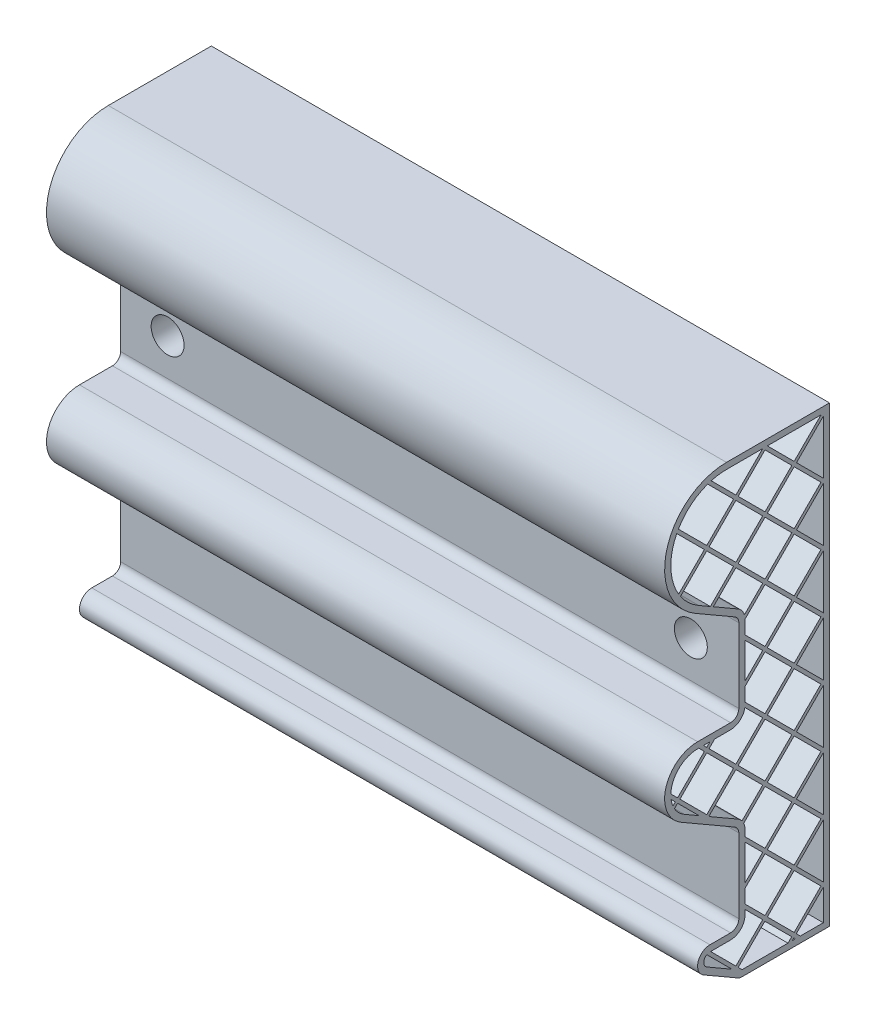
SolidWorks part; units mm, degrees
ref_plane "Front" through (0, 0, 0) normal (0, 0, 1) x (1, 0, 0)
ref_plane "Top" through (0, 0, 0) normal (0, 1, 0) x (1, 0, 0)
ref_plane "Right" through (0, 0, 0) normal (1, 0, 0) x (0, 0, -1)
sketch "Croquis1" plane through (0, 0, 0) normal (1, 0, 0) x (0, 0, -1)
  line L1 (0, 0) -> (-21.2539, 0)
  line L2 (0, 0) -> (0, 110)
  line L3 (0, 110) -> (-25, 110)
  line L5 (-32, 54.7927) -> (-24, 54.7927)
  line L10 (-22, 74.7927) -> (-22, 56.7927)
  line L14 (-22, 12.6269) -> (-22, 30.6269)
  line L16 (-36, 39.8645) -> (-23, 32.359)
  line L17 (-29, 10.6269) -> (-24, 10.6269)
  line L18 (-32.5, 82.0096) -> (-23, 76.5248)
  line L19 (-30.5, 5.0289) -> (-22.2539, 0.2679)
  arc A2 (-25, 110) -> (-32.5, 82.0096) centre (-25, 95) ccw
  arc A3 (-29, 10.6269) -> (-30.5, 5.0289) centre (-29, 7.6269) ccw
  arc A6 (-32, 54.7927) -> (-36, 39.8645) centre (-32, 46.7927) ccw
  arc A8 (-23, 76.5248) -> (-22, 74.7927) centre (-24, 74.7927) cw
  arc A9 (-22, 56.7927) -> (-24, 54.7927) centre (-24, 56.7927) cw
  arc A10 (-23, 32.359) -> (-22, 30.6269) centre (-24, 30.6269) cw
  arc A11 (-22, 12.6269) -> (-24, 10.6269) centre (-24, 12.6269) cw
  arc A12 (-21.2539, 0) -> (-22.2539, 0.2679) centre (-21.2539, 2) cw
  point P0 (0, 0)
  point P11 (-22, 54.7927)
  dimension "D1" = 2
  dimension "D2" = 15
  dimension "D8" = 8
  dimension "D9" = 30
  dimension "D12" = 2
  dimension "D7" = 2
  dimension "D10" = 2
  dimension "D11" = 2
  dimension "D16" = 18
  dimension "D19" = 110
  dimension "D14" = 10
  dimension "D6" = 3
  dimension "D3" = 40
  dimension "D4" = 30
  dimension "D5" = 18
  dimension "D13" = 30
  dimension "D17" = 20
  dimension "D18" = 20
extrude "Saliente-Extruir1" add sketch "Croquis1" along normal blind 150
sketch "Croquis2" plane through (150, 0, 0) normal (1, 0, 0) x (0, 0, -1)
  line L30 (-24, 53.2927) -> (-32, 53.2927)
  line L31 (-35.25, 41.1636) -> (-22.25, 33.658)
  line L32 (-20.5, 30.6269) -> (-20.5, 12.6269)
  line L33 (-24, 9.1269) -> (-29, 9.1269)
  line L34 (-29.75, 6.3279) -> (-21.5039, 1.567)
  line L35 (-21.2539, 1.5) -> (-1.5, 1.5)
  line L36 (-1.5, 1.5) -> (-1.5, 108.5)
  line L37 (-1.5, 108.5) -> (-25, 108.5)
  line L38 (-31.75, 83.3087) -> (-22.25, 77.8238)
  line L39 (-20.5, 74.7927) -> (-20.5, 56.7927)
  line L40 (-24, 53.2927) -> (-32, 53.2927)
  line L41 (-35.25, 41.1636) -> (-22.25, 33.658)
  line L42 (-20.5, 30.6269) -> (-20.5, 12.6269)
  line L43 (-24, 9.1269) -> (-29, 9.1269)
  line L44 (-29.75, 6.3279) -> (-21.5039, 1.567)
  line L45 (-21.2539, 1.5) -> (-1.5, 1.5)
  line L46 (-1.5, 1.5) -> (-1.5, 108.5)
  line L47 (-1.5, 108.5) -> (-25, 108.5)
  line L48 (-31.75, 83.3087) -> (-22.25, 77.8238)
  line L49 (-20.5, 74.7927) -> (-20.5, 56.7927)
  arc A24 (-24, 53.2927) -> (-20.5, 56.7927) centre (-24, 56.7927) ccw
  arc A25 (-32, 53.2927) -> (-35.25, 41.1636) centre (-32, 46.7927) ccw
  arc A26 (-20.5, 30.6269) -> (-22.25, 33.658) centre (-24, 30.6269) ccw
  arc A27 (-24, 9.1269) -> (-20.5, 12.6269) centre (-24, 12.6269) ccw
  arc A28 (-29, 9.1269) -> (-29.75, 6.3279) centre (-29, 7.6269) ccw
  arc A29 (-21.5039, 1.567) -> (-21.2539, 1.5) centre (-21.2539, 2) ccw
  arc A30 (-25, 108.5) -> (-31.75, 83.3087) centre (-25, 95) ccw
  arc A31 (-20.5, 74.7927) -> (-22.25, 77.8238) centre (-24, 74.7927) ccw
  arc A32 (-24, 53.2927) -> (-20.5, 56.7927) centre (-24, 56.7927) ccw
  arc A33 (-32, 53.2927) -> (-35.25, 41.1636) centre (-32, 46.7927) ccw
  arc A34 (-20.5, 30.6269) -> (-22.25, 33.658) centre (-24, 30.6269) ccw
  arc A35 (-24, 9.1269) -> (-20.5, 12.6269) centre (-24, 12.6269) ccw
  arc A36 (-29, 9.1269) -> (-29.75, 6.3279) centre (-29, 7.6269) ccw
  arc A37 (-21.5039, 1.567) -> (-21.2539, 1.5) centre (-21.2539, 2) ccw
  arc A38 (-25, 108.5) -> (-31.75, 83.3087) centre (-25, 95) ccw
  arc A39 (-20.5, 74.7927) -> (-22.25, 77.8238) centre (-24, 74.7927) ccw
  dimension "D1" = 1.5
sketch "Croquis3" plane through (150, 0, 0) normal (1, 0, 0) x (0, 0, -1)
  line L0 (-29.1353, 107.851) -> (-1.5, 80.2157)
  line L1 (-1.5, 108.5) -> (-25, 108.5) construction
  line L2 (-15.6421, 108.5) -> (-1.5, 94.3579)
  line L3 (-1.5, 1.5) -> (-1.5, 108.5) construction
  line L4 (-36.8654, 101.439) -> (-1.5, 66.0736)
  line L5 (-1.5, 51.9315) -> (-20.5, 70.9315)
  line L6 (-1.5, 37.7893) -> (-20.5, 56.7893)
  line L7 (-1.5, 23.6472) -> (-31.1456, 53.2927)
  line L8 (-1.5, 9.5051) -> (-38.4933, 46.4984)
  line L9 (-7.6371, 1.5) -> (-20.5, 14.3629)
  line L10 (-21.2539, 1.5) -> (-1.5, 1.5) construction
  line L11 (-20.5, 74.7927) -> (-20.5, 56.7927) construction
  line L12 (-24, 53.2927) -> (-32, 53.2927) construction
  line L13 (-20.5, 30.6269) -> (-20.5, 12.6269) construction
  line L14 (-22.3139, 2.0346) -> (-29.4062, 9.1269)
  line L15 (-29.75, 6.3279) -> (-21.5039, 1.567) construction
  line L16 (-24, 9.1269) -> (-29, 9.1269) construction
  line L17 (-1.5, 108.5) -> (-28.5429, 81.4571)
  line L18 (-36.3896, 87.7525) -> (-15.6421, 108.5)
  line L19 (-20.5397, 75.3182) -> (-1.5, 94.3579)
  line L20 (-37.8191, 43.8966) -> (-1.5, 80.2157)
  line L21 (-29.6457, 37.9279) -> (-1.5, 66.0736)
  line L22 (-20.5, 32.9315) -> (-1.5, 51.9315)
  line L23 (-31.786, 7.5034) -> (-1.5, 37.7893)
  line L24 (-22.8202, 2.327) -> (-1.5, 23.6472)
  line L25 (-9.5051, 1.5) -> (-1.5, 9.5051)
  line L26 (-31.75, 83.3087) -> (-22.25, 77.8238) construction
  line L27 (-35.25, 41.1636) -> (-22.25, 33.658) construction
  arc A0 (-25, 108.5) -> (-31.75, 83.3087) centre (-25, 95) ccw construction
  arc A1 (-24, 53.2927) -> (-20.5, 56.7927) centre (-24, 56.7927) ccw construction
  arc A2 (-32, 53.2927) -> (-35.25, 41.1636) centre (-32, 46.7927) ccw construction
  arc A3 (-20.5, 74.7927) -> (-22.25, 77.8238) centre (-24, 74.7927) ccw construction
  dimension "D1" = 45
  dimension "D2" = 10
  dimension "D4" = 10
  dimension "D5" = 10
  dimension "D6" = 10
  dimension "D7" = 10
  dimension "D8" = 10
  dimension "D9" = 10
  dimension "D10" = 10
  dimension "D11" = 45
  dimension "D12" = 10
sketch "Croquis4" plane through (150, 0, 0) normal (1, 0, 0) x (0, 0, -1)
  line L68 (-22.8202, 2.327) -> (-1.5, 23.6472) construction
  line L69 (-9.5051, 1.5) -> (-1.5, 9.5051) construction
  line L70 (-22.3139, 2.0346) -> (-29.4062, 9.1269) construction
  line L71 (-7.6371, 1.5) -> (-20.5, 14.3629) construction
  line L72 (-31.786, 7.5034) -> (-1.5, 37.7893) construction
  line L73 (-1.5, 9.5051) -> (-38.4933, 46.4984) construction
  line L74 (-1.5, 23.6472) -> (-31.1456, 53.2927) construction
  line L75 (-1.5, 37.7893) -> (-20.5, 56.7893) construction
  line L76 (-29.6457, 37.9279) -> (-1.5, 66.0736) construction
  line L77 (-1.5, 51.9315) -> (-20.5, 70.9315) construction
  line L78 (-37.8191, 43.8966) -> (-1.5, 80.2157) construction
  line L79 (-20.5397, 75.3182) -> (-1.5, 94.3579) construction
  line L80 (-1.5, 108.5) -> (-28.5429, 81.4571) construction
  line L81 (-15.6421, 108.5) -> (-1.5, 94.3579) construction
  line L82 (-36.3896, 87.7525) -> (-15.6421, 108.5) construction
  line L83 (-36.8654, 101.439) -> (-1.5, 66.0736) construction
  line L84 (-29.1353, 107.851) -> (-1.5, 80.2157) construction
  line L119 (-20.5, 32.9315) -> (-1.5, 51.9315) construction
  line L120 (-1.5, 51.9315) -> (-20.5, 70.9315)
  line L121 (-20.5, 32.9315) -> (-1.5, 51.9315)
  line L122 (-36.8654, 101.439) -> (-1.5, 66.0736)
  line L123 (-29.6457, 37.9279) -> (-1.5, 66.0736)
  line L124 (-29.1353, 107.851) -> (-1.5, 80.2157)
  line L125 (-37.8191, 43.8966) -> (-1.5, 80.2157)
  line L126 (-20.5397, 75.3182) -> (-1.5, 94.3579)
  line L127 (-15.6421, 108.5) -> (-1.5, 94.3579)
  line L128 (-36.3896, 87.7525) -> (-15.6421, 108.5)
  line L129 (-7.6371, 1.5) -> (-20.5, 14.3629)
  line L130 (-1.5, 9.5051) -> (-38.4933, 46.4984)
  line L131 (-9.5051, 1.5) -> (-1.5, 9.5051)
  line L132 (-1.5, 23.6472) -> (-31.1456, 53.2927)
  line L133 (-22.8202, 2.327) -> (-1.5, 23.6472)
  line L134 (-1.5, 37.7893) -> (-20.5, 56.7893)
  line L135 (-31.786, 7.5034) -> (-1.5, 37.7893)
  line L136 (-1.5, 108.5) -> (-28.5429, 81.4571)
  line L137 (-22.3139, 2.0346) -> (-29.4062, 9.1269)
  line L138 (-36.1068, 87.4697) -> (-15.6421, 107.9343)
  line L139 (-15.6421, 107.9343) -> (-2.0657, 94.3579)
  line L140 (-20.8225, 75.601) -> (-2.0657, 94.3579)
  line L141 (-29.4182, 107.5682) -> (-2.0657, 80.2157)
  line L142 (-38.102, 44.1794) -> (-2.0657, 80.2157)
  line L143 (-37.1483, 101.1562) -> (-1.7828, 65.7908)
  line L144 (-1.7828, 108.7828) -> (-28.8258, 81.7399)
  line L145 (-36.6725, 88.0353) -> (-15.6421, 109.0657)
  line L146 (-15.6421, 109.0657) -> (-0.9343, 94.3579)
  line L147 (-20.2568, 75.0354) -> (-0.9343, 94.3579)
  line L148 (-28.8525, 108.1339) -> (-0.9343, 80.2157)
  line L149 (-37.5363, 43.6138) -> (-0.9343, 80.2157)
  line L150 (-36.5826, 101.7219) -> (-1.2172, 66.3564)
  line L151 (-1.2172, 108.2172) -> (-28.2601, 81.1742)
  line L152 (-20.2172, 32.6486) -> (-0.9343, 51.9315)
  line L153 (-0.9343, 51.9315) -> (-20.2172, 71.2143)
  line L154 (-29.3628, 37.6451) -> (-1.2172, 65.7908)
  line L155 (-1.2172, 38.0722) -> (-20.2172, 57.0722)
  line L156 (-1.2172, 23.93) -> (-30.8627, 53.5756)
  line L157 (-20.7828, 33.2143) -> (-2.0657, 51.9315)
  line L158 (-2.0657, 51.9315) -> (-20.7828, 70.6486)
  line L159 (-29.9285, 38.2108) -> (-1.7828, 66.3564)
  line L160 (-1.7828, 37.5065) -> (-20.7828, 56.5065)
  line L161 (-1.7828, 23.3643) -> (-31.4284, 53.0099)
  line L162 (-9.2222, 1.2172) -> (-0.9343, 9.5051)
  line L163 (-0.9343, 9.5051) -> (-38.2105, 46.7812)
  line L164 (-31.5031, 7.2205) -> (-1.2172, 37.5065)
  line L165 (-22.5374, 2.0441) -> (-1.2172, 23.3643)
  line L166 (-7.3542, 1.7828) -> (-20.2172, 14.6458)
  line L167 (-22.031, 2.3175) -> (-29.1233, 9.4098)
  line L168 (-9.7879, 1.7828) -> (-2.0657, 9.5051)
  line L169 (-2.0657, 9.5051) -> (-38.7762, 46.2155)
  line L170 (-32.0688, 7.7862) -> (-1.7828, 38.0722)
  line L171 (-23.1031, 2.6098) -> (-1.7828, 23.93)
  line L172 (-7.9199, 1.2172) -> (-20.7828, 14.0801)
  line L173 (-22.5967, 1.7518) -> (-29.689, 8.8441)
  dimension "D1" = 0.4
  dimension "D2" = 0.4
  dimension "D3" = 0.4
  dimension "D4" = 0.4
  dimension "D5" = 0.4
  dimension "D6" = 0.4
sketch "Croquis5" plane through (150, 0, 0) normal (1, 0, 0) x (0, 0, -1)
  line L0 (-29.75, 6.3279) -> (-23.6523, 2.8074)
  line L1 (-9.7879, 1.7828) -> (-2.0657, 9.5051) construction
  line L2 (-22.5967, 1.7518) -> (-29.689, 8.8441) construction
  line L3 (-22.031, 2.3175) -> (-29.1233, 9.4098) construction
  line L4 (-22.5374, 2.0441) -> (-1.2172, 23.3643) construction
  line L5 (-23.1031, 2.6098) -> (-1.7828, 23.93) construction
  line L6 (-7.3542, 1.7828) -> (-20.2172, 14.6458) construction
  line L8 (-20.5, 30.6269) -> (-20.5, 29.0707)
  line L10 (-2.0657, 9.5051) -> (-38.7762, 46.2155) construction
  line L11 (-0.9343, 9.5051) -> (-38.2105, 46.7812) construction
  line L14 (-1.7828, 23.3643) -> (-31.4284, 53.0099) construction
  line L15 (-1.2172, 23.93) -> (-30.8627, 53.5756) construction
  line L16 (-1.7828, 37.5065) -> (-20.7828, 56.5065) construction
  line L17 (-1.2172, 38.0722) -> (-20.2172, 57.0722) construction
  line L18 (-29.9285, 38.2108) -> (-1.7828, 66.3564) construction
  line L19 (-29.3628, 37.6451) -> (-1.2172, 65.7908) construction
  line L20 (-0.9343, 51.9315) -> (-20.2172, 71.2143) construction
  line L21 (-2.0657, 51.9315) -> (-20.7828, 70.6486) construction
  line L22 (-37.5363, 43.6138) -> (-0.9343, 80.2157) construction
  line L23 (-38.102, 44.1794) -> (-2.0657, 80.2157) construction
  line L24 (-20.2568, 75.0354) -> (-0.9343, 94.3579) construction
  line L25 (-20.8225, 75.601) -> (-2.0657, 94.3579) construction
  line L26 (-1.2172, 108.2172) -> (-28.2601, 81.1742) construction
  line L27 (-1.7828, 108.7828) -> (-28.8258, 81.7399) construction
  line L28 (-15.6421, 107.9343) -> (-2.0657, 94.3579) construction
  line L29 (-15.6421, 109.0657) -> (-0.9343, 94.3579) construction
  line L30 (-36.1068, 87.4697) -> (-15.6421, 107.9343) construction
  line L31 (-36.6725, 88.0353) -> (-15.6421, 109.0657) construction
  line L32 (-37.1483, 101.1562) -> (-1.7828, 65.7908) construction
  line L33 (-36.5826, 101.7219) -> (-1.2172, 66.3564) construction
  line L34 (-28.8525, 108.1339) -> (-0.9343, 80.2157) construction
  line L35 (-29.4182, 107.5682) -> (-2.0657, 80.2157) construction
  line L37 (-10.0707, 1.5) -> (-9.1719, 2.3988)
  line L38 (-23.6523, 2.8074) -> (-29.7632, 8.9183)
  line L39 (-21.2135, 1.5) -> (-22.1475, 2.434)
  line L40 (-22.1475, 2.434) -> (-15.6773, 8.9042)
  line L41 (-22.7132, 2.9997) -> (-16.2078, 9.5051)
  line L42 (-7.0714, 1.5) -> (-8.0499, 2.4785)
  line L46 (-2.0657, 9.5051) -> (-8.5711, 16.0104)
  line L47 (-1.5, 10.0707) -> (-8.0054, 16.5761)
  line L50 (-2.0657, 23.6472) -> (-8.5711, 30.1526)
  line L51 (-1.5, 24.2129) -> (-8.0054, 30.7183)
  line L52 (-2.0657, 37.7893) -> (-8.5711, 44.2947)
  line L53 (-1.5, 38.355) -> (-8.0054, 44.8604)
  line L54 (-29.7843, 38.355) -> (-23.2789, 44.8604)
  line L55 (-29.2186, 37.7893) -> (-22.7132, 44.2947)
  line L56 (-1.5, 52.4971) -> (-8.0054, 59.0025)
  line L57 (-2.0657, 51.9315) -> (-8.5711, 58.4368)
  line L58 (-37.6211, 43.5289) -> (-36.8553, 44.2947)
  line L59 (-37.9967, 44.2847) -> (-37.421, 44.8604)
  line L60 (-20.5, 74.7922) -> (-15.6421, 79.65)
  line L61 (-20.6424, 75.7811) -> (-16.2078, 80.2157)
  line L62 (-1.5, 107.9343) -> (-8.0054, 101.4289)
  line L63 (-2.0657, 108.5) -> (-8.5711, 101.9946)
  line L64 (-15.6421, 107.9343) -> (-9.1368, 101.4289)
  line L65 (-15.0765, 108.5) -> (-8.5711, 101.9946)
  line L66 (-36.1652, 87.4113) -> (-29.7843, 93.7922)
  line L67 (-36.6051, 88.1027) -> (-30.35, 94.3579)
  line L68 (-37.0596, 101.0675) -> (-30.35, 94.3579)
  line L69 (-36.6617, 101.801) -> (-29.7843, 94.9235)
  line L70 (-28.7013, 107.9827) -> (-22.7132, 101.9946)
  line L71 (-29.5574, 107.7075) -> (-23.2789, 101.4289)
  line L72 (-22.7132, 101.9946) -> (-16.2078, 108.5)
  line L73 (-22.1475, 101.4289) -> (-15.6421, 94.9235)
  line L74 (-22.1475, 101.4289) -> (-15.6421, 107.9343)
  line L75 (-22.7132, 100.8632) -> (-16.2078, 94.3579)
  line L76 (-29.7843, 94.9235) -> (-23.2789, 101.4289)
  line L77 (-29.7843, 93.7922) -> (-23.2789, 87.2868)
  line L78 (-29.2186, 94.3579) -> (-22.7132, 87.8525)
  line L79 (-29.2186, 94.3579) -> (-22.7132, 100.8632)
  line L80 (-16.2078, 94.3579) -> (-22.7132, 87.8525)
  line L81 (-15.0765, 94.3579) -> (-8.5711, 87.8525)
  line L82 (-15.6421, 93.7922) -> (-22.1475, 87.2868)
  line L83 (-15.6421, 93.7922) -> (-9.1368, 87.2868)
  line L84 (-9.1368, 101.4289) -> (-15.6421, 94.9235)
  line L85 (-8.0054, 101.4289) -> (-1.5, 94.9235)
  line L86 (-8.5711, 100.8632) -> (-2.0657, 94.3579)
  line L87 (-8.5711, 100.8632) -> (-15.0765, 94.3579)
  line L88 (-8.5711, 87.8525) -> (-2.0657, 94.3579)
  line L89 (-8.0054, 87.2868) -> (-1.5, 80.7814)
  line L90 (-8.0054, 87.2868) -> (-1.5, 93.7922)
  line L91 (-8.5711, 86.7211) -> (-2.0657, 80.2157)
  line L92 (-23.2789, 87.2868) -> (-28.9016, 81.6641)
  line L93 (-22.7132, 86.7211) -> (-16.2078, 80.2157)
  line L94 (-22.1475, 87.2868) -> (-15.6421, 80.7814)
  line L95 (-22.7132, 86.7211) -> (-28.1843, 81.25)
  line L96 (-15.6421, 80.7814) -> (-9.1368, 87.2868)
  line L97 (-15.6421, 79.65) -> (-9.1368, 73.1447)
  line L98 (-15.0765, 80.2157) -> (-8.5711, 73.7103)
  line L99 (-15.0765, 80.2157) -> (-8.5711, 86.7211)
  line L100 (-8.5711, 73.7103) -> (-2.0657, 80.2157)
  line L101 (-8.5711, 72.579) -> (-2.0657, 66.0736)
  line L102 (-8.0054, 73.1447) -> (-1.5, 66.6393)
  line L103 (-8.0054, 73.1447) -> (-1.5, 79.65)
  line L104 (-15.6421, 66.6393) -> (-9.1368, 73.1447)
  line L105 (-16.2078, 66.0736) -> (-20.5, 70.3658)
  line L106 (-15.6421, 66.6393) -> (-20.5, 71.4971)
  line L107 (-15.0765, 66.0736) -> (-8.5711, 72.579)
  line L108 (-8.5711, 59.5682) -> (-2.0657, 66.0736)
  line L109 (-9.1368, 59.0025) -> (-15.6421, 65.5079)
  line L110 (-8.5711, 59.5682) -> (-15.0765, 66.0736)
  line L111 (-8.0054, 59.0025) -> (-1.5, 65.5079)
  line L112 (-15.6421, 52.4971) -> (-9.1368, 59.0025)
  line L113 (-15.6421, 52.4971) -> (-20.5, 57.355)
  line L114 (-16.2078, 51.9315) -> (-20.5402, 56.2638)
  line L115 (-15.0765, 51.9315) -> (-8.5711, 58.4368)
  line L116 (-29.7843, 52.4971) -> (-28.9887, 53.2927)
  line L117 (-30.35, 51.9315) -> (-31.7112, 53.2927)
  line L118 (-29.7843, 52.4971) -> (-30.5799, 53.2927)
  line L119 (-29.2186, 51.9315) -> (-27.8573, 53.2927)
  line L120 (-36.8553, 45.4261) -> (-30.35, 51.9315)
  line L121 (-37.421, 44.8604) -> (-38.4348, 45.8741)
  line L122 (-36.8553, 45.4261) -> (-38.4943, 47.065)
  line L123 (-36.2897, 44.8604) -> (-29.7843, 51.3658)
  line L124 (-29.7843, 38.355) -> (-36.2897, 44.8604)
  line L125 (-21.2303, 32.7668) -> (-16.2078, 37.7893)
  line L129 (-15.6421, 38.355) -> (-9.1368, 44.8604)
  line L130 (-15.6421, 38.355) -> (-22.1475, 44.8604)
  line L131 (-15.0765, 37.7893) -> (-8.5711, 44.2947)
  line L132 (-16.2078, 37.7893) -> (-22.7132, 44.2947)
  line L133 (-8.5711, 31.2839) -> (-2.0657, 37.7893)
  line L134 (-8.5711, 31.2839) -> (-15.0765, 37.7893)
  line L135 (-8.0054, 30.7183) -> (-1.5, 37.2236)
  line L136 (-9.1368, 30.7183) -> (-15.6421, 37.2236)
  line L137 (-15.6421, 24.2129) -> (-9.1368, 30.7183)
  line L138 (-15.6421, 24.2129) -> (-20.5, 29.0707)
  line L139 (-15.0765, 23.6472) -> (-8.5711, 30.1526)
  line L140 (-16.2078, 23.6472) -> (-20.5, 27.9394)
  line L141 (-8.5711, 17.1418) -> (-2.0657, 23.6472)
  line L142 (-8.5711, 17.1418) -> (-15.0765, 23.6472)
  line L143 (-8.0054, 16.5761) -> (-1.5, 23.0815)
  line L144 (-9.1368, 16.5761) -> (-15.6421, 23.0815)
  line L145 (-20.5, 19.355) -> (-16.2078, 23.6472)
  line L149 (-15.6421, 10.0707) -> (-9.1368, 16.5761)
  line L150 (-15.6421, 10.0707) -> (-20.5, 14.9286)
  line L151 (-16.2078, 9.5051) -> (-20.5, 13.7972)
  line L152 (-15.0765, 9.5051) -> (-8.5711, 16.0104)
  line L153 (-8.5711, 2.9997) -> (-2.0657, 9.5051)
  line L154 (-9.1719, 2.3988) -> (-15.6773, 8.9042)
  line L155 (-8.5711, 2.9997) -> (-15.0765, 9.5051)
  line L156 (-8.0499, 2.4785) -> (-1.5, 8.9394)
  line L157 (-22.7132, 2.9997) -> (-28.8405, 9.1269)
  line L162 (-8.5711, 45.4261) -> (-2.0657, 51.9315)
  line L163 (-8.0054, 44.8604) -> (-1.5, 51.3658)
  line L164 (-8.5711, 45.4261) -> (-15.0765, 51.9315)
  line L165 (-9.1368, 44.8604) -> (-15.6421, 51.3658)
  line L166 (-22.7132, 45.4261) -> (-16.2078, 51.9315)
  line L167 (-23.2789, 44.8604) -> (-29.7843, 51.3658)
  line L168 (-22.7132, 45.4261) -> (-29.2186, 51.9315)
  line L169 (-22.1475, 44.8604) -> (-15.6421, 51.3658)
  line L170 (-16.2078, 108.5) -> (-25, 108.5)
  line L171 (-1.5, 94.9235) -> (-1.5, 107.9343)
  line L172 (-1.5, 80.7814) -> (-1.5, 93.7922)
  line L173 (-1.5, 66.6393) -> (-1.5, 79.65)
  line L174 (-1.5, 52.4971) -> (-1.5, 65.5079)
  line L175 (-1.5, 38.355) -> (-1.5, 51.3658)
  line L176 (-1.5, 24.2129) -> (-1.5, 37.2236)
  line L177 (-1.5, 10.0707) -> (-1.5, 23.0815)
  line L178 (-7.0714, 1.5) -> (-1.5, 1.5)
  line L180 (-31.75, 83.3087) -> (-22.25, 77.8238)
  line L181 (-20.5, 74.7927) -> (-20.5, 56.7927)
  line L182 (-24, 53.2927) -> (-32, 53.2927)
  line L183 (-35.25, 41.1636) -> (-22.25, 33.658)
  line L184 (-20.5, 30.6269) -> (-20.5, 12.6269)
  line L185 (-24, 9.1269) -> (-29, 9.1269)
  line L186 (-29.75, 6.3279) -> (-21.5039, 1.567)
  line L187 (-21.2539, 1.5) -> (-1.5, 1.5)
  line L188 (-1.5, 1.5) -> (-1.5, 108.5)
  line L189 (-1.5, 108.5) -> (-25, 108.5)
  line L190 (-31.75, 83.3087) -> (-28.9016, 81.6641)
  line L192 (-24, 53.2927) -> (-27.8573, 53.2927)
  line L193 (-35.25, 41.1636) -> (-31.6399, 39.0793)
  line L195 (-24, 9.1269) -> (-28.8405, 9.1269)
  line L197 (-21.2135, 1.5) -> (-10.0707, 1.5)
  line L198 (-1.5, 1.5) -> (-1.5, 8.9394)
  line L199 (-2.0657, 108.5) -> (-15.0765, 108.5)
  line L200 (-20.5, 18.2236) -> (-20.5, 14.9286)
  line L201 (-8.6549, 1.8818) -> (-8.2731, 1.5)
  line L202 (-8.2731, 1.5) -> (-9.0419, 1.5)
  line L203 (-8.6549, 1.8818) -> (-9.0419, 1.5)
  line L206 (-31.6399, 39.0793) -> (-36.8553, 44.2947)
  line L207 (-28.9631, 37.5338) -> (-29.2186, 37.7893)
  line L209 (-28.9631, 37.5338) -> (-22.25, 33.658)
  line L210 (-28.1843, 81.25) -> (-22.25, 77.8238)
  line L211 (-20.5, 70.3658) -> (-20.5, 61.7814)
  line L212 (-20.5, 61.7814) -> (-16.2078, 66.0736)
  line L213 (-20.5, 60.65) -> (-15.6421, 65.5079)
  line L214 (-20.5, 60.65) -> (-20.5, 57.355)
  line L215 (-28.9887, 53.2927) -> (-30.5799, 53.2927)
  line L216 (-31.7112, 53.2927) -> (-32, 53.2927)
  line L217 (-20.5, 74.7922) -> (-20.5, 71.4971)
  line L218 (-15.6421, 37.2236) -> (-20.8065, 32.0593)
  line L219 (-20.5, 27.9394) -> (-20.5, 19.355)
  line L221 (-20.5, 18.2236) -> (-15.6421, 23.0815)
  line L222 (-20.5, 13.7972) -> (-20.5, 12.6269)
  arc A0 (-29.5574, 107.7075) -> (-36.6617, 101.801) centre (-25, 95) ccw
  arc A1 (-37.0596, 101.0675) -> (-36.6051, 88.1027) centre (-25, 95) ccw
  arc A2 (-36.1652, 87.4113) -> (-31.75, 83.3087) centre (-25, 95) ccw
  arc A3 (-38.4348, 45.8741) -> (-37.9967, 44.2847) centre (-32, 46.7927) ccw
  arc A4 (-37.6211, 43.5289) -> (-35.25, 41.1636) centre (-32, 46.7927) ccw
  arc A5 (-21.2303, 32.7668) -> (-22.25, 33.658) centre (-24, 30.6269) ccw
  arc A8 (-20.5, 74.7927) -> (-22.25, 77.8238) centre (-24, 74.7927) ccw
  arc A9 (-24, 53.2927) -> (-20.5, 56.7927) centre (-24, 56.7927) ccw
  arc A10 (-32, 53.2927) -> (-35.25, 41.1636) centre (-32, 46.7927) ccw
  arc A11 (-20.5, 30.6269) -> (-22.25, 33.658) centre (-24, 30.6269) ccw
  arc A12 (-24, 9.1269) -> (-20.5, 12.6269) centre (-24, 12.6269) ccw
  arc A13 (-29, 9.1269) -> (-29.75, 6.3279) centre (-29, 7.6269) ccw
  arc A14 (-21.5039, 1.567) -> (-21.2539, 1.5) centre (-21.2539, 2) ccw
  arc A15 (-25, 108.5) -> (-31.75, 83.3087) centre (-25, 95) ccw
  arc A16 (-20.6424, 75.7811) -> (-22.25, 77.8238) centre (-24, 74.7927) ccw
  arc A17 (-24, 53.2927) -> (-20.5402, 56.2638) centre (-24, 56.7927) ccw
  arc A18 (-32, 53.2927) -> (-38.4943, 47.065) centre (-32, 46.7927) ccw
  arc A19 (-20.5, 30.6269) -> (-20.8065, 32.0593) centre (-24, 30.6269) ccw
  arc A20 (-24, 9.1269) -> (-20.5, 12.6269) centre (-24, 12.6269) ccw
  arc A21 (-29.7632, 8.9183) -> (-29.75, 6.3279) centre (-29, 7.6269) ccw
  arc A23 (-25, 108.5) -> (-28.7013, 107.9827) centre (-25, 95) ccw
  dimension "D1" = 0
extrude "Cortar-Extruir1" cut sketch "Croquis5" against normal through all
sketch "Croquis6" plane through (0, 0, 22) normal (0, 0, 1) x (1, 0, 0)
  line L0 (0, 65.7927) -> (150, 65.7927) construction
  line L1 (0, 74.7927) -> (0, 56.7927) construction
  line L2 (150, 74.7927) -> (150, 56.7927) construction
  circle A0 centre (11.3917, 65.7927) radius 5
  circle A1 centre (138.3593, 65.7927) radius 5
  dimension "D1" = 10
  dimension "D2" = 10
extrude "Saliente-Extruir2" add sketch "Croquis6" against normal up to surface (22 mm away) contours A0 up to face at (75, 55, 0)
extrude "Saliente-Extruir3" add sketch "Croquis6<3>" against normal up to surface (22 mm away) contours A1 up to face at (75, 55, 0)
sketch "Croquis6<3>" plane through (0, 0, 22) normal (0, 0, 1) x (1, 0, 0) same geometry as "Croquis6"
sketch "Croquis7" plane through (0, 0, 22) normal (0, 0, 1) x (1, 0, 0)
  circle A0 centre (11.3917, 65.7927) radius 2.5
  circle A1 centre (138.3593, 65.7927) radius 2.567
  dimension "D1" = 5
  dimension "D2" = 5.134
extrude "Cortar-Extruir2" cut sketch "Croquis7" against normal up to surface (22 mm away) up to face at (75, 55, 0)
sketch "Croquis8" plane through (0, 0, 22) normal (0, 0, 1) x (1, 0, 0)
  circle A0 centre (11.3917, 65.7927) radius 4
  circle A1 centre (138.3593, 65.7927) radius 4
  dimension "D1" = 8
  dimension "D2" = 8
extrude "Cortar-Extruir3" cut sketch "Croquis8" against normal blind 7
sketch "Croquis9" plane through (0, 0, 0) normal (0, 0, -1) x (-1, 0, 0)
  text T0 "V2"
extrude "Cortar-Extruir4" cut sketch "Croquis9" against normal blind 0.5
